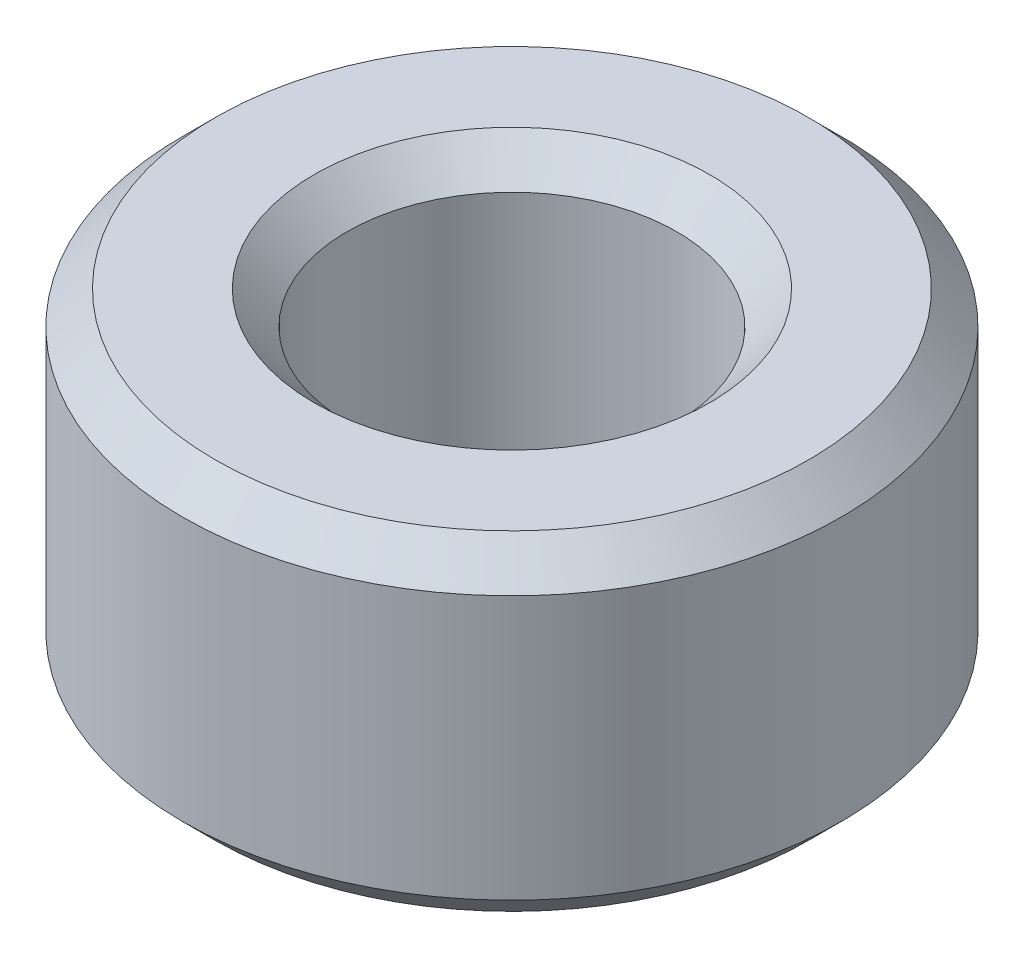
SolidWorks part; units mm, degrees
ref_plane "Front Plane" through (0, 0, 0) normal (0, 0, 1) x (1, 0, 0)
ref_plane "Top Plane" through (0, 0, 0) normal (0, 1, 0) x (1, 0, 0)
ref_plane "Right Plane" through (0, 0, 0) normal (1, 0, 0) x (0, 0, -1)
sketch "Sketch1" plane through (0, 0, 0) normal (0, 1, 0) x (1, 0, 0)
  circle A0 centre (0, 0) radius 10
  dimension "SLEEVE_OD" = 20
extrude "Boss-Extrude1" add sketch "Sketch1" along normal blind 10
sketch "Sketch2" plane through (0, 0, 0) normal (0, 1, 0) x (1, 0, 0)
  circle A0 centre (0, 0) radius 5
  dimension "BORE_D" = 10
extrude "Cut-Extrude1" cut sketch "Sketch2" along normal through all
chamfer "Chamfer1" distance 1 angle 45 4 edges at (0, 10, 5) (0, 0, 5) (0, 0, 10) (0, 10, 10)
